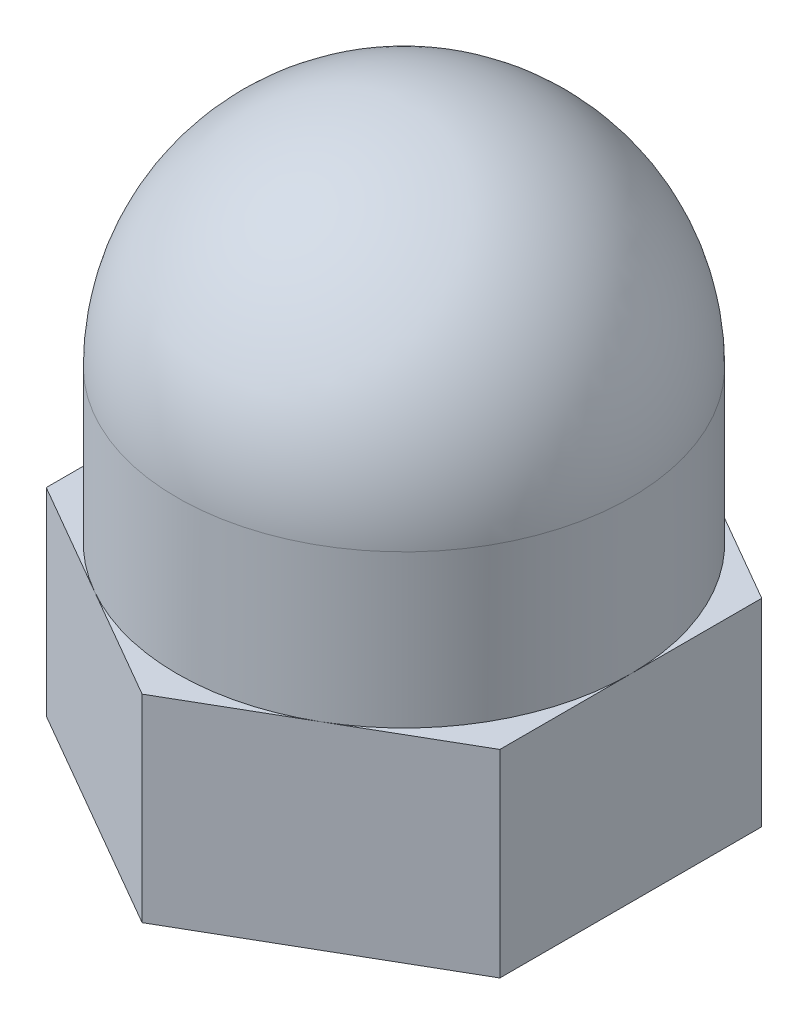
SolidWorks part; units mm, degrees
ref_plane "Płaszczyzna przednia" through (0, 0, 0) normal (0, 0, 1) x (1, 0, 0)
ref_plane "Płaszczyzna górna" through (0, 0, 0) normal (0, 1, 0) x (1, 0, 0)
ref_plane "Płaszczyzna prawa" through (0, 0, 0) normal (1, 0, 0) x (0, 0, -1)
sketch "Szkic1" plane through (0, 0, 0) normal (0, 1, 0) x (1, 0, 0)
  line L1 (0, 3.1754) -> (-2.75, 1.5877)
  line L2 (-2.75, 1.5877) -> (-2.75, -1.5877)
  line L3 (-2.75, -1.5877) -> (0, -3.1754)
  line L4 (0, -3.1754) -> (2.75, -1.5877)
  line L5 (2.75, -1.5877) -> (2.75, 1.5877)
  line L6 (2.75, 1.5877) -> (0, 3.1754)
  circle A0 centre (0, 0) radius 2.75 construction
  circle A1 centre (0, 0) radius 1.5
  dimension "D1" = 3
  dimension "D2" = 5.5
extrude "Dodanie-wyciągnięcie1" add sketch "Szkic1" along normal blind 2.4
sketch "Szkic3" plane through (0, 0, 0) normal (0, 0, 1) x (1, 0, 0)
  line L0 (0, 2.4) -> (0, 7.742) construction
  line L1 (-2.75, 2.4) -> (-2.75, 4.25)
  line L2 (-2.75, 2.4) -> (0, 2.4) construction
  line L3 (2.75, 2.4) -> (2.75, 4.25)
  line L4 (0, 2.4) -> (2.75, 2.4) construction
  line L6 (0, 7) -> (-2.75, 7) construction
  line L7 (-2.75, 0) -> (0, 0) construction
  line L8 (-2.75, 2.4) -> (2.75, 2.4)
  line L9 (0, 7) -> (0, 2.4)
  arc A0 (-2.75, 4.25) -> (2.75, 4.25) centre (0, 4.25) cw
  dimension "D2" = 7
  dimension "D1" = 5.5
revolve "Obrót2" add sketch "Szkic3" angle 360 about L9 region at (1.263, 4.4519, 0)
